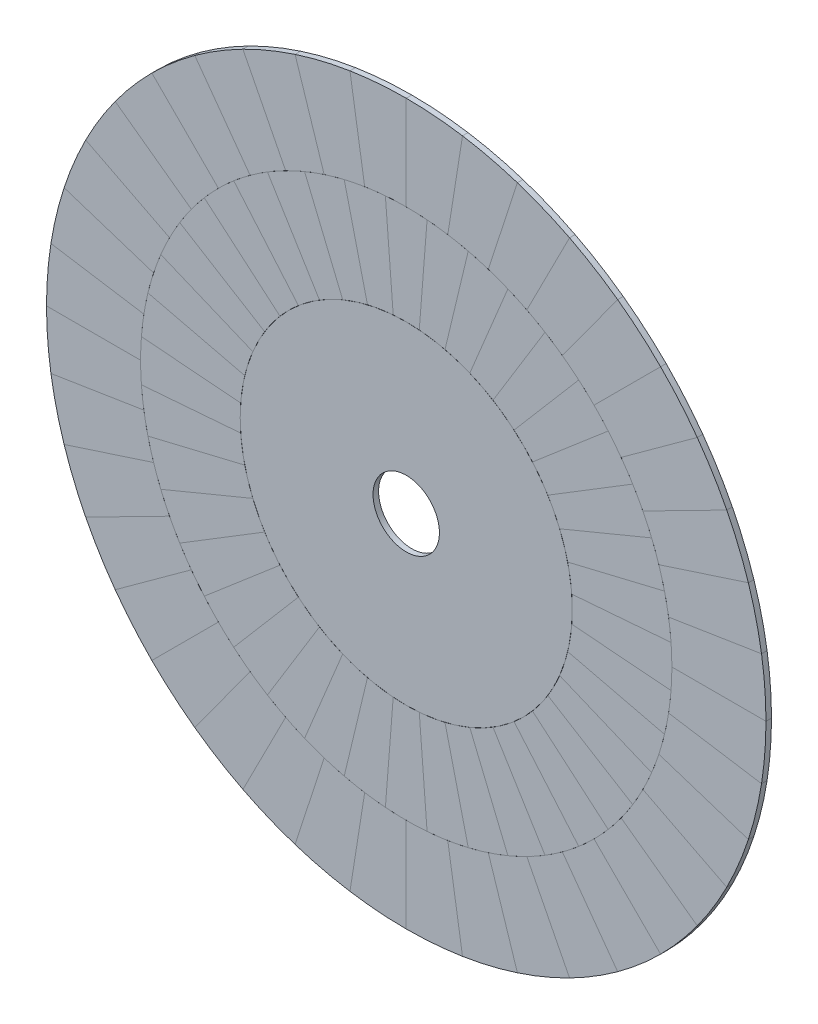
SolidWorks part; units mm, degrees
ref_plane "Front Plane" through (0, 0, 0) normal (0, 0, 1) x (1, 0, 0)
ref_plane "Top Plane" through (0, 0, 0) normal (0, 1, 0) x (1, 0, 0)
ref_plane "Right Plane" through (0, 0, 0) normal (1, 0, 0) x (0, 0, -1)
sketch "Sketch1" plane through (0, 0, 0) normal (0, 0, 1) x (1, 0, 0)
  line L0 (24, 0) -> (32.5, 0)
  line L1 (23.7045, -3.7544) -> (32.0999, -5.0841)
  line L2 (22.8254, -7.4164) -> (30.9093, -10.0431)
  line L3 (21.3842, -10.8958) -> (28.9577, -14.7547)
  line L4 (19.4164, -14.1068) -> (26.2931, -19.103)
  line L5 (16.9706, -16.9706) -> (22.981, -22.981)
  line L6 (14.1068, -19.4164) -> (19.103, -26.2931)
  line L7 (10.8958, -21.3842) -> (14.7547, -28.9577)
  line L8 (7.4164, -22.8254) -> (10.0431, -30.9093)
  line L9 (3.7544, -23.7045) -> (5.0841, -32.0999)
  line L10 (0, -24) -> (0, -32.5)
  line L11 (-3.7544, -23.7045) -> (-5.0841, -32.0999)
  line L12 (-7.4164, -22.8254) -> (-10.0431, -30.9093)
  line L13 (-10.8958, -21.3842) -> (-14.7547, -28.9577)
  line L14 (-14.1068, -19.4164) -> (-19.103, -26.2931)
  line L15 (-16.9706, -16.9706) -> (-22.981, -22.981)
  line L16 (-19.4164, -14.1068) -> (-26.2931, -19.103)
  line L17 (-21.3842, -10.8958) -> (-28.9577, -14.7547)
  line L18 (-22.8254, -7.4164) -> (-30.9093, -10.0431)
  line L19 (-23.7045, -3.7544) -> (-32.0999, -5.0841)
  line L20 (-24, 0) -> (-32.5, 0)
  line L21 (-23.7045, 3.7544) -> (-32.0999, 5.0841)
  line L22 (-22.8254, 7.4164) -> (-30.9093, 10.0431)
  line L23 (-21.3842, 10.8958) -> (-28.9577, 14.7547)
  line L24 (-19.4164, 14.1068) -> (-26.2931, 19.103)
  line L25 (-16.9706, 16.9706) -> (-22.981, 22.981)
  line L26 (-14.1068, 19.4164) -> (-19.103, 26.2931)
  line L27 (-10.8958, 21.3842) -> (-14.7547, 28.9577)
  line L28 (-7.4164, 22.8254) -> (-10.0431, 30.9093)
  line L29 (-3.7544, 23.7045) -> (-5.0841, 32.0999)
  line L30 (0, 24) -> (0, 32.5)
  line L31 (3.7544, 23.7045) -> (5.0841, 32.0999)
  line L32 (7.4164, 22.8254) -> (10.0431, 30.9093)
  line L33 (10.8958, 21.3842) -> (14.7547, 28.9577)
  line L34 (14.1068, 19.4164) -> (19.103, 26.2931)
  line L35 (16.9706, 16.9706) -> (22.981, 22.981)
  line L36 (19.4164, 14.1068) -> (26.2931, 19.103)
  line L37 (21.3842, 10.8958) -> (28.9577, 14.7547)
  line L38 (22.8254, 7.4164) -> (30.9093, 10.0431)
  line L39 (23.7045, 3.7544) -> (32.0999, 5.0841)
  line L40 (14.9538, 1.1769) -> (23.926, 1.883)
  line L41 (14.9538, -1.1769) -> (23.926, -1.883)
  line L42 (14.5855, -3.5017) -> (23.3369, -5.6027)
  line L43 (13.8582, -5.7403) -> (22.1731, -9.1844)
  line L44 (12.7896, -7.8375) -> (20.4634, -12.54)
  line L45 (11.4061, -9.7417) -> (18.2497, -15.5868)
  line L46 (9.7417, -11.4061) -> (15.5868, -18.2497)
  line L47 (7.8375, -12.7896) -> (12.54, -20.4634)
  line L48 (5.7403, -13.8582) -> (9.1844, -22.1731)
  line L49 (3.5017, -14.5855) -> (5.6027, -23.3369)
  line L50 (1.1769, -14.9538) -> (1.883, -23.926)
  line L51 (-1.1769, -14.9538) -> (-1.883, -23.926)
  line L52 (-3.5017, -14.5855) -> (-5.6027, -23.3369)
  line L53 (-5.7403, -13.8582) -> (-9.1844, -22.1731)
  line L54 (-7.8375, -12.7896) -> (-12.54, -20.4634)
  line L55 (-9.7417, -11.4061) -> (-15.5868, -18.2497)
  line L56 (-11.4061, -9.7417) -> (-18.2497, -15.5868)
  line L57 (-12.7896, -7.8375) -> (-20.4634, -12.54)
  line L58 (-13.8582, -5.7403) -> (-22.1731, -9.1844)
  line L59 (-14.5855, -3.5017) -> (-23.3369, -5.6027)
  line L60 (-14.9538, -1.1769) -> (-23.926, -1.883)
  line L61 (-14.9538, 1.1769) -> (-23.926, 1.883)
  line L62 (-14.5855, 3.5017) -> (-23.3369, 5.6027)
  line L63 (-13.8582, 5.7403) -> (-22.1731, 9.1844)
  line L64 (-12.7896, 7.8375) -> (-20.4634, 12.54)
  line L65 (-11.4061, 9.7417) -> (-18.2497, 15.5868)
  line L66 (-9.7417, 11.4061) -> (-15.5868, 18.2497)
  line L67 (-7.8375, 12.7896) -> (-12.54, 20.4634)
  line L68 (-5.7403, 13.8582) -> (-9.1844, 22.1731)
  line L69 (-3.5017, 14.5855) -> (-5.6027, 23.3369)
  line L70 (-1.1769, 14.9538) -> (-1.883, 23.926)
  line L71 (1.1769, 14.9538) -> (1.883, 23.926)
  line L72 (3.5017, 14.5855) -> (5.6027, 23.3369)
  line L73 (5.7403, 13.8582) -> (9.1844, 22.1731)
  line L74 (7.8375, 12.7896) -> (12.54, 20.4634)
  line L75 (9.7417, 11.4061) -> (15.5868, 18.2497)
  line L76 (11.4061, 9.7417) -> (18.2497, 15.5868)
  line L77 (12.7896, 7.8375) -> (20.4634, 12.54)
  line L78 (13.8582, 5.7403) -> (22.1731, 9.1844)
  line L79 (14.5855, 3.5017) -> (23.3369, 5.6027)
  circle A0 centre (0, 0) radius 32.5
  circle A1 centre (0, 0) radius 24
  circle A2 centre (0, 0) radius 15
  circle A3 centre (0, 0) radius 3
  point P46 (0, 0)
  point P128 (0, 0)
  dimension "D1" = 65
  dimension "D3" = 48
  dimension "D6" = 30
  dimension "D7" = 6
  dimension "D4" = 4.5
  dimension "D2" = 40
  dimension "D5" = 40
extrude "Boss-Extrude1" add sketch "Sketch1" along normal blind 0.5 contours A1 L34 A0 L33 | A1 L36 A0 L35 | A1 L38 A0 L37 | A1 L0 A0 L39 | A1 L2 A0 L1 | A1 L4 A0 L3 | A1 L6 A0 L5 | A1 L8 A0 L7 | A1 L10 A0 L9 | A1 L12 A0 L11 | A1 L14 A0 L13 | A1 L16 A0 L15 | A1 L18 A0 L17 | A1 L20 A0 L19 | A1 L22 A0 L21 | A1 L24 A0 L23 | A1 L26 A0 L25 | A1 L28 A0 L27 | A1 L30 A0 L29 | A1 L32 A0 L31 region at (28.3462, 2.2309, 0) region at (27.6482, -6.6378, 0) region at (26.2695, 10.8812, 0) region at (24.2439, -14.8567, 0) region at (21.6213, 18.4663, 0) region at (18.4663, -21.6213, 0) region at (14.8567, 24.2439, 0) region at (10.8812, -26.2695, 0) region at (6.6378, 27.6482, 0) region at (2.2309, -28.3462, 0) region at (-2.2309, 28.3462, 0) region at (-6.6378, -27.6482, 0) region at (-10.8812, 26.2695, 0) region at (-14.8567, -24.2439, 0) region at (-18.4663, 21.6213, 0) region at (-21.6213, -18.4663, 0) region at (-24.2439, 14.8567, 0) region at (-26.2695, -10.8812, 0) region at (-27.6482, 6.6378, 0) region at (-28.3462, -2.2309, 0)
extrude "Boss-Extrude2" add sketch "Sketch1<3>" along normal blind 0.5 separate body contours A1 L25 A0 L24 | A1 L27 A0 L26 | A1 L29 A0 L28 | A1 L31 A0 L30 | A1 L33 A0 L32 | A1 L35 A0 L34 | A1 L37 A0 L36 | A1 L39 A0 L38 | A1 L1 A0 L0 | A1 L3 A0 L2 | A1 L5 A0 L4 | A1 L7 A0 L6 | A1 L9 A0 L8 | A1 L11 A0 L10 | A1 L13 A0 L12 | A1 L15 A0 L14 | A1 L17 A0 L16 | A1 L19 A0 L18 | A1 L21 A0 L20 | A1 L23 A0 L22 region at (28.3462, -2.2309, 0) region at (27.6482, 6.6378, 0) region at (26.2695, -10.8812, 0) region at (24.2439, 14.8567, 0) region at (21.6213, -18.4663, 0) region at (18.4663, 21.6213, 0) region at (14.8567, -24.2439, 0) region at (10.8812, 26.2695, 0) region at (6.6378, -27.6482, 0) region at (2.2309, 28.3462, 0) region at (-2.2309, -28.3462, 0) region at (-6.6378, 27.6482, 0) region at (-10.8812, -26.2695, 0) region at (-14.8567, 24.2439, 0) region at (-18.4663, -21.6213, 0) region at (-21.6213, 18.4663, 0) region at (-24.2439, -14.8567, 0) region at (-26.2695, 10.8812, 0) region at (-27.6482, -6.6378, 0) region at (-28.3462, 2.2309, 0)
sketch "Sketch1<3>" plane through (0, 0, 0) normal (0, 0, 1) x (1, 0, 0) same geometry as "Sketch1"
extrude "Boss-Extrude3" add sketch "Sketch1<4>" along normal blind 0.5 separate body contours A2 L41 A1 L40 | A2 L79 A1 L78 | A2 L77 A1 L76 | A2 L75 A1 L74 | A2 L73 A1 L72 | A2 L71 A1 L70 | A2 L69 A1 L68 | A2 L67 A1 L66 | A2 L65 A1 L64 | A2 L63 A1 L62 | A2 L61 A1 L60 | A2 L59 A1 L58 | A2 L57 A1 L56 | A2 L55 A1 L54 | A2 L53 A1 L52 | A2 L51 A1 L50 | A2 L49 A1 L48 | A2 L47 A1 L46 | A2 L45 A1 L44 | A2 L43 A1 L42 region at (19.8258, 0, 0) region at (18.8554, 6.1265, 0) region at (18.8554, -6.1265, 0) region at (16.0394, 11.6533, 0) region at (16.0394, -11.6533, 0) region at (11.6533, 16.0394, 0) region at (11.6533, -16.0394, 0) region at (6.1265, 18.8554, 0) region at (6.1265, -18.8554, 0) region at (0, 19.8258, 0) region at (0, -19.8258, 0) region at (-6.1265, 18.8554, 0) region at (-6.1265, -18.8554, 0) region at (-11.6533, 16.0394, 0) region at (-11.6533, -16.0394, 0) region at (-16.0394, 11.6533, 0) region at (-16.0394, -11.6533, 0) region at (-18.8554, 6.1265, 0) region at (-18.8554, -6.1265, 0) region at (-19.8258, 0, 0)
sketch "Sketch1<4>" plane through (0, 0, 0) normal (0, 0, 1) x (1, 0, 0) same geometry as "Sketch1"
extrude "Boss-Extrude4" add sketch "Sketch1<5>" along normal blind 0.5 separate body contours A2 L68 A1 L67 | A2 L70 A1 L69 | A2 L72 A1 L71 | A2 L74 A1 L73 | A2 L76 A1 L75 | A2 L78 A1 L77 | A2 L40 A1 L79 | A2 L42 A1 L41 | A2 L44 A1 L43 | A2 L46 A1 L45 | A2 L48 A1 L47 | A2 L50 A1 L49 | A2 L52 A1 L51 | A2 L54 A1 L53 | A2 L56 A1 L55 | A2 L58 A1 L57 | A2 L60 A1 L59 | A2 L62 A1 L61 | A2 L64 A1 L63 | A2 L66 A1 L65 region at (19.5817, 3.1014, 0) region at (19.5817, -3.1014, 0) region at (17.6649, 9.0007, 0) region at (17.6649, -9.0007, 0) region at (14.0189, 14.0189, 0) region at (14.0189, -14.0189, 0) region at (9.0007, 17.6649, 0) region at (9.0007, -17.6649, 0) region at (3.1014, 19.5817, 0) region at (3.1014, -19.5817, 0) region at (-3.1014, 19.5817, 0) region at (-3.1014, -19.5817, 0) region at (-9.0007, 17.6649, 0) region at (-9.0007, -17.6649, 0) region at (-14.0189, 14.0189, 0) region at (-14.0189, -14.0189, 0) region at (-17.6649, 9.0007, 0) region at (-17.6649, -9.0007, 0) region at (-19.5817, 3.1014, 0) region at (-19.5817, -3.1014, 0)
sketch "Sketch1<5>" plane through (0, 0, 0) normal (0, 0, 1) x (1, 0, 0) same geometry as "Sketch1"
extrude "Boss-Extrude6" add sketch "Sketch1<9>" along normal blind 0.5 separate body contours A2 A3 region at (14.5645, 0.5722, 0)
sketch "Sketch1<9>" plane through (0, 0, 0) normal (0, 0, 1) x (1, 0, 0) same geometry as "Sketch1"
